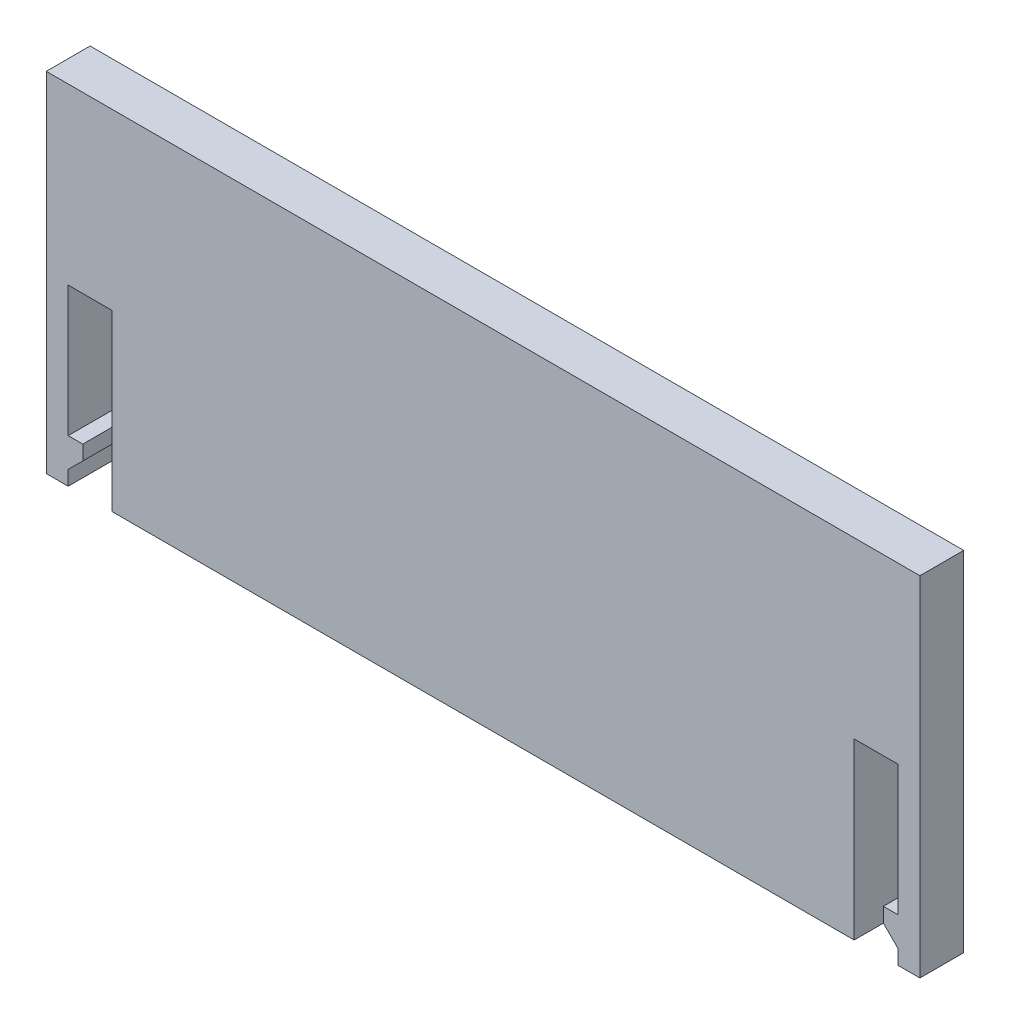
SolidWorks part; units mm, degrees
ref_plane "Front Plane" through (0, 0, 0) normal (0, 0, 1) x (1, 0, 0)
ref_plane "Top Plane" through (0, 0, 0) normal (0, 1, 0) x (1, 0, 0)
ref_plane "Right Plane" through (0, 0, 0) normal (1, 0, 0) x (0, 0, -1)
sketch "Sketch1" plane through (0, 0, 0) normal (0, 0, 1) x (1, 0, 0)
  line L0 (-50.8, -26.2747) -> (-50.8, -23.2747) construction
  line L1 (-50.8, -23.2747) -> (-53.8, -23.2747) construction
  line L2 (-53.8, -23.2747) -> (-53.8, -26.2747) construction
  line L3 (-53.8, -26.2747) -> (-50.8, -26.2747) construction
  line L4 (-50.8, -14.3504) -> (-50.8, -2.426) construction
  line L5 (-50.8, -2.426) -> (-53.8, -2.426) construction
  line L6 (-53.8, -2.426) -> (-53.8, -14.3504) construction
  line L7 (-53.8, -14.3504) -> (-50.8, -14.3504) construction
  line L8 (3, -26.2747) -> (3, -23.2747) construction
  line L9 (3, -23.2747) -> (0, -23.2747) construction
  line L10 (0, -23.2747) -> (0, -26.2747) construction
  line L11 (0, -26.2747) -> (3, -26.2747) construction
  line L12 (3, -14.3504) -> (3, -2.426) construction
  line L13 (3, -2.426) -> (0, -2.426) construction
  line L14 (0, -2.426) -> (0, -14.3504) construction
  line L15 (0, -14.3504) -> (3, -14.3504) construction
  line L16 (-50.8, -26.2747) -> (-50.8, -23.2747) construction
  line L17 (-50.8, -23.2747) -> (-53.8, -23.2747) construction
  line L18 (-53.8, -23.2747) -> (-53.8, -26.2747) construction
  line L19 (-53.8, -26.2747) -> (-50.8, -26.2747) construction
  line L20 (-50.8, -14.3504) -> (-50.8, -2.426) construction
  line L21 (-50.8, -2.426) -> (-53.8, -2.426) construction
  line L22 (-53.8, -2.426) -> (-53.8, -14.3504) construction
  line L23 (-53.8, -14.3504) -> (-50.8, -14.3504) construction
  line L24 (3, -26.2747) -> (3, -23.2747) construction
  line L25 (3, -23.2747) -> (0, -23.2747) construction
  line L26 (0, -23.2747) -> (0, -26.2747) construction
  line L27 (0, -26.2747) -> (3, -26.2747) construction
  line L28 (3, -14.3504) -> (3, -2.426) construction
  line L29 (3, -2.426) -> (0, -2.426) construction
  line L30 (0, -2.426) -> (0, -14.3504) construction
  line L31 (0, -14.3504) -> (3, -14.3504) construction
  line L33 (-55.3, -2.426) -> (4.5, -2.426)
  line L34 (-55.3, -2.426) -> (-55.3, -26.2747)
  line L35 (-55.3, -26.2747) -> (4.5, -26.2747)
  line L36 (4.5, -2.426) -> (4.5, -26.2747)
  line L37 (-55.3, -2.426) -> (4.5, -26.2747) construction
  line L38 (-55.3, -26.2747) -> (4.5, -2.426) construction
  line L39 (-53.8, -14.3504) -> (-50.8, -14.3504)
  line L40 (-53.8, -14.3504) -> (-53.8, -23.2747)
  line L41 (-53.8, -23.2747) -> (-50.8, -23.2747)
  line L42 (-50.8, -14.3504) -> (-50.8, -23.2747)
  line L43 (0, -14.3504) -> (3, -14.3504)
  line L44 (0, -14.3504) -> (0, -23.2747)
  line L45 (0, -23.2747) -> (3, -23.2747)
  line L46 (3, -14.3504) -> (3, -23.2747)
  point P2 (-25.4, -14.3504)
  dimension "D1" = 1.5
  dimension "D2" = 1.5
extrude "Boss-Extrude1" add sketch "Sketch1" along normal blind 3
sketch "Sketch2" plane through (0, 0, 3) normal (0, 0, 1) x (1, 0, 0)
  line L0 (-55.3, -26.2747) -> (4.5, -26.2747) construction
  line L1 (-53.8, -23.2747) -> (-50.8, -23.2747)
  line L2 (-53.8, -23.2747) -> (-53.8, -26.2747)
  line L3 (-53.8, -26.2747) -> (-50.8, -26.2747)
  line L4 (-50.8, -23.2747) -> (-50.8, -26.2747)
  line L5 (-50.8, -23.2747) -> (-50.8, -14.3504) construction
  line L6 (-53.8, -23.2747) -> (-52.8, -23.2747)
  line L7 (-52.8, -23.2747) -> (-52.8, -24.2747)
  line L8 (-52.8, -24.2747) -> (-53.8, -25.2747)
  line M11 (-55.3, -26.2747) -> (4.5, -26.2747)
  line M14 (-50.8, -23.2747) -> (-53.8, -23.2747)
  dimension "D1" = 1
  dimension "D2" = 1
  dimension "D3" = 135
extrude "Cut-Extrude1" cut sketch "Sketch2" against normal through all contours L7 L8 L2 L4 M11 M14 region at (-52.0889, -24.9192, 3)
ref_plane "Plane1" through (-25.4, 0, 0) normal (-1, 0, 0) x (0, 0, 1)
mirror "Mirror1" about plane through (-25.4, 0, 0) normal (-1, 0, 0) of "Cut-Extrude1"
sketch "Sketch4" plane through (0, 0, 0) normal (0, 0, -1) x (-1, 0, 0)
  line L0 (-4.5, -2.426) -> (55.3, -26.2747) construction
  line L1 (3.175, -6.0954) -> (47.625, -6.0954)
  line L2 (3.175, -6.0954) -> (3.175, -22.6054)
  line L3 (3.175, -22.6054) -> (47.625, -22.6054)
  line L4 (47.625, -6.0954) -> (47.625, -22.6054)
  line L5 (3.175, -6.0954) -> (47.625, -22.6054) construction
  line L6 (3.175, -22.6054) -> (47.625, -6.0954) construction
  point P0 (25.4, -14.3504)
  point P9 (25.4, -14.3504)
  point P10 (39.35, -6.5456)
  dimension "D1" = 44.45
  dimension "D2" = 16.51
extrude "Cut-Extrude2" cut sketch "Sketch4" against normal blind 1
sketch "Sketch5" plane through (0, 0, 1) normal (0, 0, -1) x (-1, 0, 0)
  line L0 (3.175, -6.0954) -> (3.825, -6.0954)
  line L1 (47.625, -6.0954) -> (3.175, -6.0954) construction
  line L2 (3.175, -6.0954) -> (3.175, -7.3954)
  line L3 (3.175, -6.0954) -> (3.175, -22.6054) construction
  arc A0 (3.175, -7.3954) -> (3.825, -6.0954) centre (4.8, -7.3954) cw
  dimension "D1" = 0.65
  dimension "D2" = 1.3
extrude "Boss-Extrude2" add sketch "Sketch5" along normal up to surface (1 mm away) up to face at (-25.4, -14.3504, 0)
ref_plane "Plane2" through (0, -14.3504, 0) normal (0, 1, 0) x (1, 0, 0)
mirror "Mirror2" about plane through (-25.4, 0, 0) normal (-1, 0, 0) of "Boss-Extrude2" second plane through (0, -14.3504, 0) second plane normal (0, 1, 0)
equation "\"thick\"= 3mm"
equation "\"D1@Boss-Extrude1\"=\"thick\""
